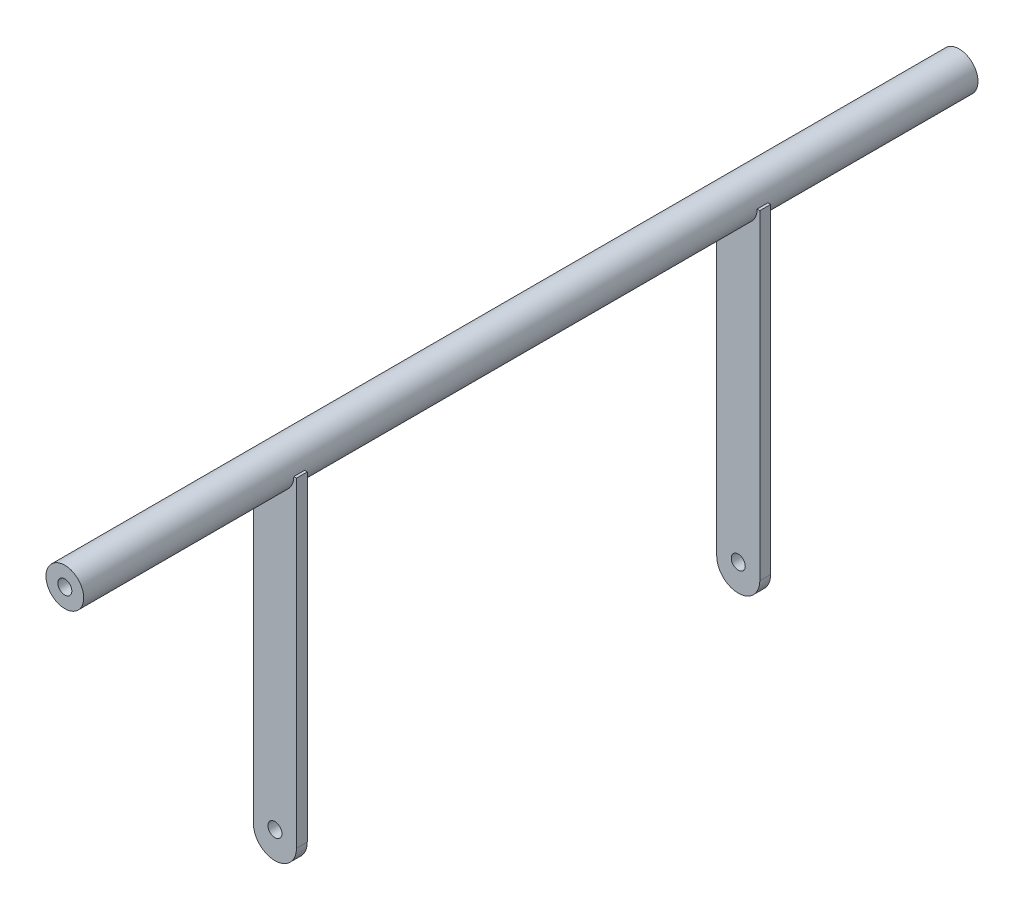
SolidWorks part; units mm, degrees
ref_plane "Front Plane" through (0, 0, 0) normal (0, 0, 1) x (1, 0, 0)
ref_plane "Top Plane" through (0, 0, 0) normal (0, 1, 0) x (1, 0, 0)
ref_plane "Right Plane" through (0, 0, 0) normal (1, 0, 0) x (0, 0, -1)
sketch "Sketch1" plane through (0, 0, 0) normal (0, 0, 1) x (1, 0, 0)
  circle A0 centre (0, 0) radius 17.5
  dimension "D1" = 35
extrude "Boss-Extrude1" add sketch "Sketch1" along normal mid plane 830
sketch "Sketch2" plane through (0, 0, 415) normal (0, 0, 1) x (1, 0, 0)
  circle A0 centre (0, 0) radius 6.5
  dimension "D1" = 13
extrude "Cut-Extrude1" cut sketch "Sketch2" against normal up to next
sketch "Sketch3" plane through (0, 0, 0) normal (1, 0, 0) x (0, 0, -1)
  line L0 (-415, 0) -> (415, 0) construction
  line L1 (-415, 17.5) -> (-415, -17.5) construction
  line L2 (415, -17.5) -> (415, 17.5) construction
  line L3 (0, 301.5209) -> (0, -360.8541) construction
  line L4 (-220, 0) -> (-210, 0)
  line L5 (-220, 0) -> (-220, -317.5)
  line L6 (-220, -317.5) -> (-210, -317.5)
  line L7 (-210, 0) -> (-210, -317.5)
  line L8 (-415, -17.5) -> (415, -17.5) construction
  line L9 (210, 0) -> (210, -317.5)
  line L10 (220, -317.5) -> (210, -317.5)
  line L11 (220, 0) -> (220, -317.5)
  line L12 (220, 0) -> (210, 0)
  dimension "D1" = 440
  dimension "D2" = 10
  dimension "D3" = 300
extrude "Boss-Extrude2" add sketch "Sketch3" along normal mid plane 40
fillet "Fillet1" radius 20 4 edges at (-20, -317.5, -215) (20, -317.5, -215) (-20, -317.5, 215) (20, -317.5, 215)
sketch "Sketch4" plane through (0, 0, 220) normal (0, 0, 1) x (1, 0, 0)
  line L0 (0, -248.627) -> (0, -317.5) construction
  circle A0 centre (0, -292.5) radius 6.5
  dimension "D1" = 13
  dimension "D2" = 25
extrude "Cut-Extrude2" cut sketch "Sketch4" against normal blind 542
